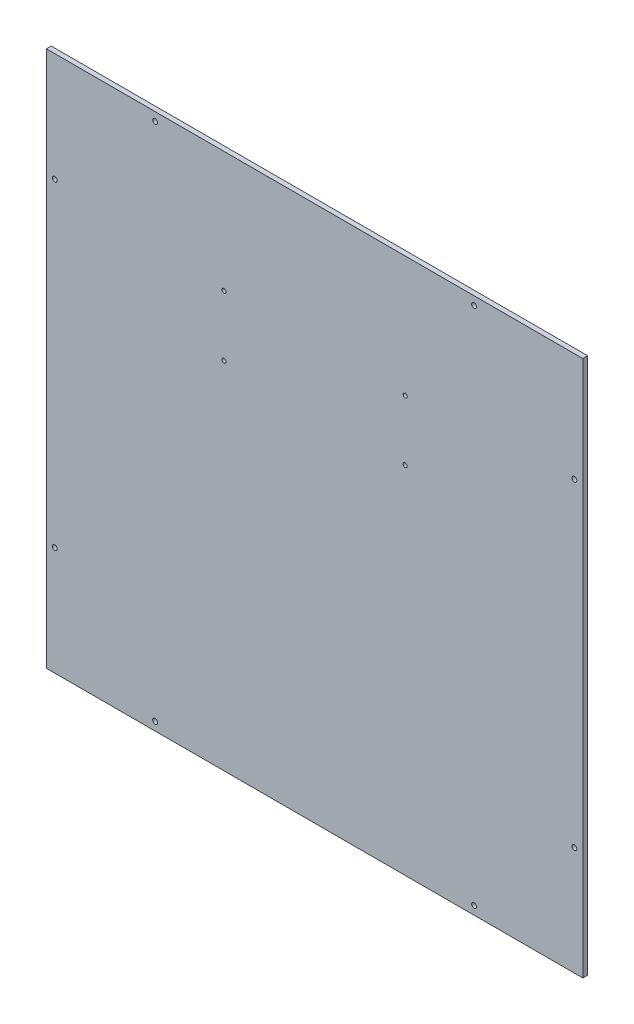
SolidWorks part; units mm, degrees
ref_plane "Piano frontale" through (0, 0, 0) normal (0, 0, 1) x (1, 0, 0)
ref_plane "Piano superiore" through (0, 0, 0) normal (0, 1, 0) x (1, 0, 0)
ref_plane "Piano destro" through (0, 0, 0) normal (1, 0, 0) x (0, 0, -1)
sketch "Schizzo1" plane through (0, 0, 0) normal (0, 0, 1) x (1, 0, 0)
  line L0 (0, 0) -> (0, 444)
  line L1 (0, 444) -> (444, 444)
  line L2 (444, 444) -> (444, 0)
  line L3 (444, 0) -> (0, 0)
  line L4 (0, 222) -> (444, 222) construction
  line L5 (222, 42) -> (222, 123.488) construction
  circle A0 centre (90, 437) radius 2
  circle A1 centre (354, 437) radius 2
  circle A2 centre (437, 354) radius 2
  circle A3 centre (7, 354) radius 2
  circle A4 centre (437, 90) radius 2
  circle A5 centre (354, 7) radius 2
  circle A6 centre (90, 7) radius 2
  circle A7 centre (7, 90) radius 2
  dimension "D3" = 4
  dimension "D4" = 7
  dimension "D6" = 7
  dimension "D5" = 90
  dimension "D1" = 444
  dimension "D2" = 444
  dimension "D7" = 90
extrude "Estrusione-Estrusione1" add sketch "Schizzo1" along normal blind 4
sketch "Schizzo2" plane through (0, 0, 4) normal (0, 0, 1) x (1, 0, 0)
  line L1 (444, 444) -> (0, 444) construction
  line L2 (222, 444) -> (222, 0) construction
  line L3 (0, 0) -> (444, 0) construction
  circle A0 centre (147, 344) radius 1.7
  circle A1 centre (147, 294) radius 1.7
  circle A2 centre (297, 344) radius 1.7
  circle A3 centre (297, 294) radius 1.7
  dimension "D1" = 150
  dimension "D2" = 100
  dimension "D3" = 3.4
  dimension "D4" = 50
extrude "Taglio-Estrusione1" cut sketch "Schizzo2" against normal through all
